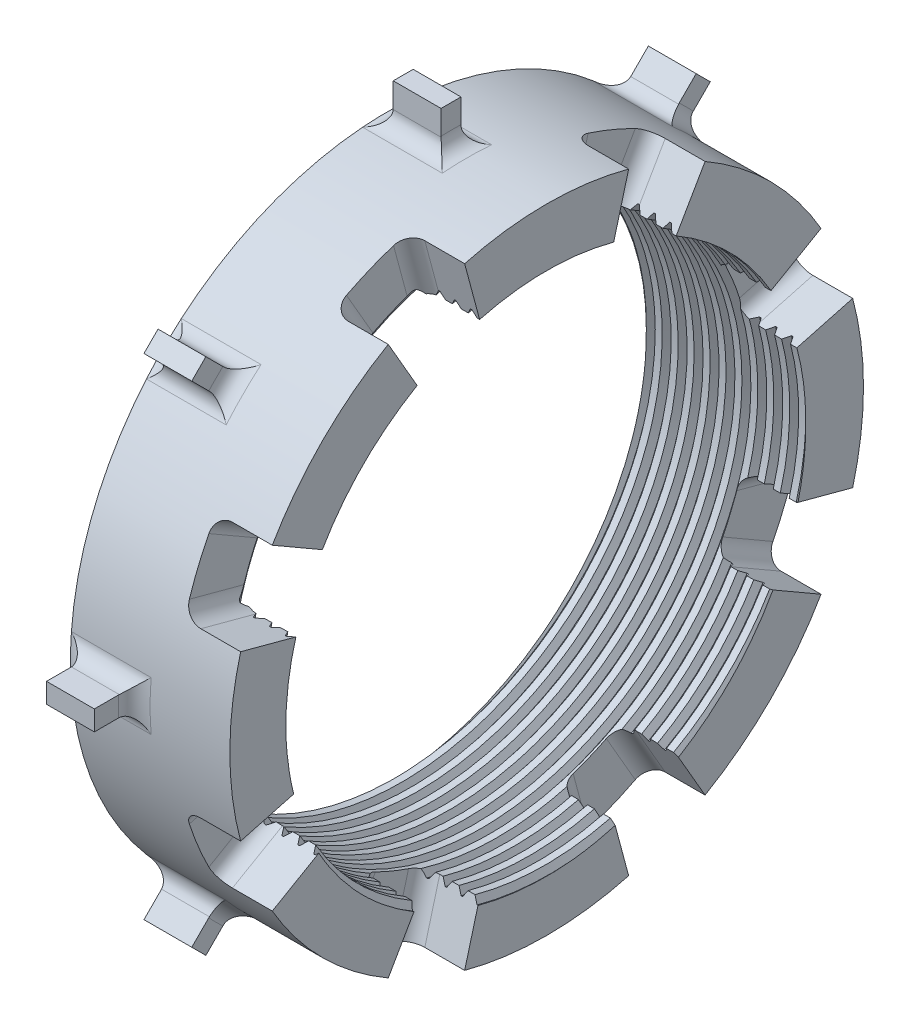
SolidWorks part; units mm, degrees
material "6061-T6 (SS)"
ref_plane "Front Plane" through (0, 0, 0) normal (0, 0, 1) x (1, 0, 0)
ref_plane "Top Plane" through (0, 0, 0) normal (0, 1, 0) x (1, 0, 0)
ref_plane "Right Plane" through (0, 0, 0) normal (1, 0, 0) x (0, 0, -1)
ref_plane "Plane4" through (8, 0, 0) normal (1, 0, 0) x (0, 0, -1)
sketch "Sketch1" plane through (0, 0, 0) normal (1, 0, 0) x (0, 0, -1)
  circle A0 centre (0, 0) radius 32.5
  circle A1 centre (0, 0) radius 39.75
  dimension "D1" = 65
  dimension "D2" = 7.25
extrude "Boss-Extrude1" add sketch "Sketch1" along normal blind 20
sketch "Sketch2" plane through (8, 0, 0) normal (1, 0, 0) x (0, 0, -1)
  line L1 (39.7303, 1.25) -> (44.75, 1.25)
  line L3 (39.7303, -1.25) -> (44.75, -1.25)
  line L4 (44.75, 1.25) -> (44.75, -1.25)
  line L5 (39.75, 0) -> (44.75, -1.25) construction
  line L6 (39.75, 0) -> (44.75, 1.25) construction
  arc A1 (39.7303, -1.25) -> (39.7303, 1.25) centre (0, 0) ccw
  circle A2 centre (0, 0) radius 39.75
  circle A3 centre (0, 0) radius 39.75
  point P0 (39.75, 0)
  dimension "D1" = 0
  dimension "D2" = 2.5
  dimension "D3" = 5
extrude "Boss-Extrude2" add sketch "Sketch2" against normal blind 6 contours L1 L4 L3 A1
ref_axis "Axis1" through (20, 0, 0) along (-1, 0, 0)
pattern_circular "CirPattern1" count 8 over 360 about axis through (20, 0, 0) along (-1, 0, 0) of "Boss-Extrude2"
fillet "Fillet1" radius 2 32 edges at (5, 39.7303, 1.25) (5, 39.7303, -1.25) (5, 28.9775, 27.2097) (5, 27.2097, 28.9775) (5, -1.25, 39.7303) (5, 1.25, 39.7303) (5, -27.2097, 28.9775) (5, -28.9775, 27.2097) (5, -39.7303, -1.25) (5, -39.7303, 1.25) (5, -28.9775, -27.2097) (5, -1.25, -39.7303) (5, -27.2097, -28.9775) (5, 1.25, -39.7303) (5, 27.2097, -28.9775) (5, 28.9775, -27.2097) (2, 28.1075, -28.1075) (2, 39.75, 0) (2, 28.1075, 28.1075) (2, 0, 39.75) (2, -28.1075, 28.1075) (2, -39.75, 0) (2, -28.1075, -28.1075) (2, 0, -39.75) (8, 39.75, 0) (8, 28.1075, -28.1075) (8, 0, -39.75) (8, -28.1075, -28.1075) (8, -39.75, 0) (8, -28.1075, 28.1075) (8, 0, 39.75) (8, 28.1075, 28.1075)
ref_plane "Plane5" through (20, 0, 0) normal (1, 0, 0) x (0, 0, -1)
sketch "Sketch3" plane through (20, 0, 0) normal (1, 0, 0) x (0, 0, -1)
  line L3 (0, 0) -> (36.7242, -15.2117) construction
  line L6 (0, 0) -> (34.4245, -19.875)
  line L7 (0, 0) -> (38.3956, -10.2881)
  circle A0 centre (0, 0) radius 39.75 construction
  circle A1 centre (0, 0) radius 39.75
  point P6 (0, 0)
  point P31 (0, 0)
  point P39 (0, 0)
  dimension "D1" = 7.5
extrude "Cut-Extrude2" cut sketch "Sketch3" against normal blind 7 contours L7 L3 A1 | L3 L6 A1 region at (20, -8.5121, -25.0757) region at (20, -11.7123, -23.7502)
fillet "Fillet2" radius 2 2 edges at (13, -18.0625, -31.2852) (13, -9.3498, -34.8941)
pattern_circular "CirPattern2" count 8 over 360 about axis through (20, 0, 0) along (-1, 0, 0) of "Cut-Extrude2", "Fillet2"
thread "Thread1" pitch 1.5 method cut trim with start face yes profile "Thread Profile2" start angle 0, offset 2, length 25, pitch 2, diameter 65
ref_plane "Plane3" through (-2, 0, -32.5) normal (0, -1, 0) x (0, 0, -1)
sketch "Thread Profile2" plane through (-2, 0, -32.5) normal (0, -1, 0) x (0, 0, -1)
  line L0 (0, 0) -> (0, 1.5) construction
  line L1 (0, 0) -> (0.8119, 0.4687)
  line L2 (0.8119, 0.4687) -> (0.8119, 0.6562)
  line L3 (0.8119, 0.6562) -> (0, 1.125)
  line L4 (0.8119, 0.5625) -> (0, 0.5625) construction
  line L11 (0, 0) -> (0, 1.125)
  point P2 (0, 0)
  dimension "Pitch" = 1.5
  dimension "Profile_Angle" = 60
  dimension "Profile_Land" = 0.1875
  dimension "Profile_Height" = 0.8119
